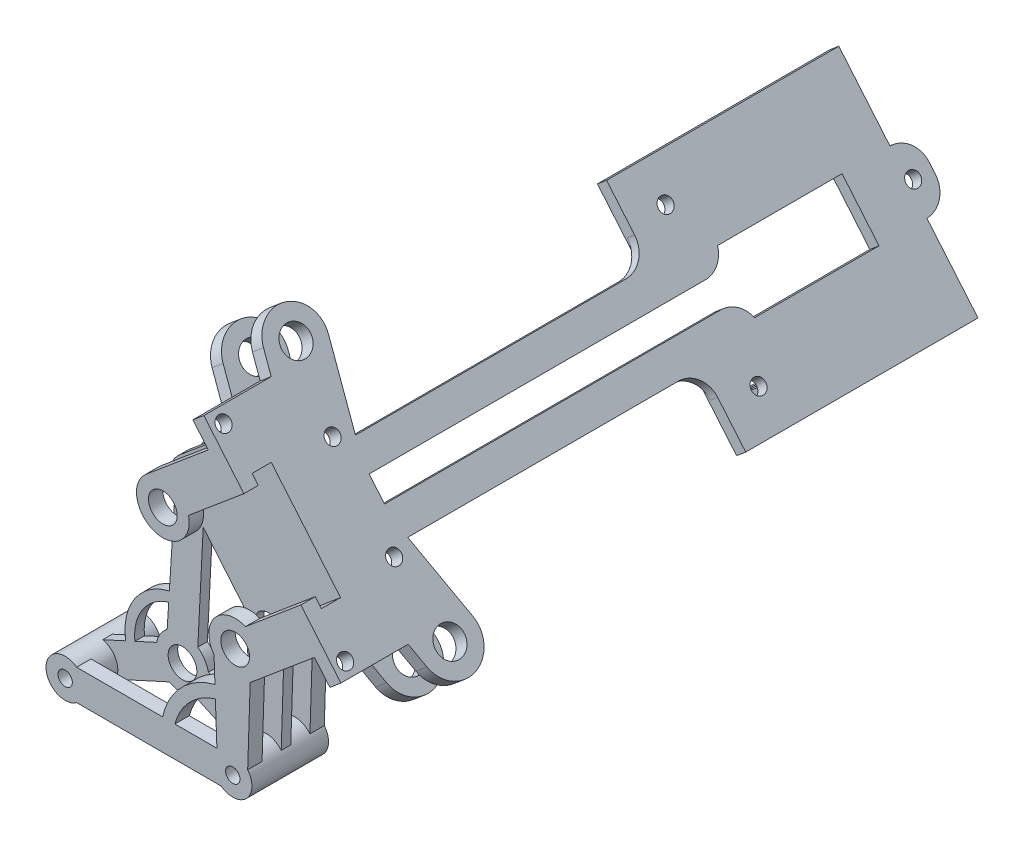
SolidWorks part; units mm, degrees
ref_plane "Front Plane" through (0, 0, 0) normal (0, 0, 1) x (1, 0, 0)
ref_plane "Top Plane" through (0, 0, 0) normal (0, 1, 0) x (1, 0, 0)
ref_plane "Right Plane" through (0, 0, 0) normal (1, 0, 0) x (0, 0, -1)
sketch "Sketch1" plane through (0, 0, 0) normal (0, 0, 1) x (1, 0, 0)
  line L0 (0, 0) -> (0, 8) construction
  line L1 (0, 8) -> (18.002, 23.1055) construction
  line L2 (2.8965, 41.1076) -> (18.002, 23.1055) construction
  circle A1 centre (2.8965, 41.1076) radius 3
  circle A3 centre (0, 8) radius 2.5
  circle A4 centre (-17.5, 0) radius 2.1
  circle A5 centre (17.5, 0) radius 2.1
  circle A6 centre (18.002, 23.1055) radius 3
  dimension "D1" = 5
  dimension "D2" = 8
  dimension "D5" = 6
  dimension "D6" = 6
  dimension "D3" = 50
  dimension "D4" = 23.5
  dimension "D7" = 23.5
  dimension "D8" = 90
sketch "Sketch2" plane through (0, 0, 0) normal (0, 0, 1) x (1, 0, 0)
  circle A0 centre (-17.5, 0) radius 4
  circle A1 centre (17.5, 0) radius 4
  circle A2 centre (17.5, 0) radius 1.5
  circle A3 centre (-17.5, 0) radius 1.5
  dimension "D2" = 8
  dimension "D3" = 8
  dimension "D4" = 3
  dimension "D5" = 3
extrude "Boss-Extrude1" add sketch "Sketch2" along normal blind 7
sketch "Sketch3" plane through (0, 0, 7) normal (0, 0, 1) x (1, 0, 0)
  line L0 (21.5374, 18.8923) -> (36.8583, 31.748)
  line L1 (36.8583, 31.748) -> (14.6821, 58.1765)
  line L2 (14.6821, 58.1765) -> (-0.6388, 45.3208)
  line L3 (2.8965, 41.1076) -> (18.002, 23.1055) construction
  line L4 (12.7408, 24.7084) -> (4.3263, 34.7365)
  line L5 (21.8764, 27.0092) -> (29.9374, 33.7731)
  line L6 (8.1578, 39.5046) -> (17.3371, 28.5652)
  line L7 (29.9374, 33.7731) -> (15.4746, 51.0091)
  line L8 (15.4746, 51.0091) -> (7.4137, 44.2452)
  line L9 (18.002, 23.1055) -> (17.5, 0) construction
  line L10 (21.1372, 18.5866) -> (20.6119, 2.5132)
  line L11 (13.4856, 19.9667) -> (14.1163, 5.0654)
  line L13 (-3.2, 12.4733) -> (-2.8753, 17.5777)
  line L14 (3.2, 12.4733) -> (4.3263, 34.7365)
  line L15 (0, 8) -> (17.5, 0) construction
  line L16 (5.3987, 9.0505) -> (14.1163, 5.0654)
  line L17 (2.7379, 3.2299) -> (13.9868, -1.9125)
  line L18 (-17.5, 0) -> (0, 8) construction
  line L19 (-16.6477, 3.9081) -> (-11.8489, 6.1019)
  line L20 (-13.9868, -1.9125) -> (-2.7379, 3.2299)
  line L21 (-9.947, 6.9713) -> (-5.3987, 9.0505)
  line L22 (-2.7414, 19.6827) -> (-1.5817, 37.9146)
  circle A0 centre (18.002, 23.1055) radius 3
  circle A2 centre (0, 8) radius 3
  arc A3 (12.7408, 24.7084) -> (13.4856, 19.9667) centre (18.002, 23.1055) ccw
  arc A4 (5.3987, 9.0505) -> (3.2, 12.4733) centre (0, 8) ccw
  arc A5 (8.1578, 39.5046) -> (7.4137, 44.2452) centre (2.8965, 41.1076) ccw
  circle A6 centre (17.5, 0) radius 4 construction
  circle A7 centre (-17.5, 0) radius 4 construction
  arc A8 (13.9868, -1.9125) -> (20.6119, 2.5132) centre (17.5, 0) ccw
  arc A9 (-16.6477, 3.9081) -> (-13.9868, -1.9125) centre (-17.5, 0) ccw
  circle A10 centre (-17.5, 0) radius 1.5 construction
  circle A11 centre (17.5, 0) radius 1.5 construction
  circle A12 centre (-17.5, 0) radius 1.5
  circle A13 centre (17.5, 0) radius 1.5
  arc A22 (-2.7414, 19.6827) -> (-11.8489, 6.1019) centre (0, 8) ccw
  arc A23 (-2.8753, 17.5777) -> (-9.947, 6.9713) centre (0, 8) ccw
  arc A24 (-3.2, 12.4733) -> (-5.3987, 9.0505) centre (0, 8) ccw
  circle A25 centre (0, 8) radius 5.5 construction
  arc A26 (-2.7379, 3.2299) -> (2.7379, 3.2299) centre (0, 8) ccw
  arc A27 (-0.6388, 45.3208) -> (-1.5817, 37.9146) centre (2.8965, 41.1076) ccw
  circle A28 centre (2.8965, 41.1076) radius 3
  circle A29 centre (18.002, 23.1055) radius 5.5 construction
  arc A30 (21.8764, 27.0092) -> (17.3371, 28.5652) centre (18.002, 23.1055) ccw
  arc A31 (21.1372, 18.5866) -> (21.5374, 18.8923) centre (18.002, 23.1055) ccw
  point P14 (22.117, 24.617)
  point P26 (5.5, 41.234)
  point P33 (5.5, 8)
  point P41 (17.0585, 12.3085)
  point P46 (0, 24.617)
  point P51 (8.75, 4)
  point P57 (-8.75, 4)
  circle M4 centre (17.5, 0) radius 4
  circle M5 centre (17.5, 0) radius 1.5
  dimension "D1" = 6
  dimension "D2" = 6
  dimension "D3" = 6
  dimension "D17" = 10
  dimension "D18" = 12
  dimension "D7" = 3
  dimension "D8" = 3
  dimension "D9" = 4
  dimension "D10" = 6
  dimension "D11" = 6
  dimension "D12" = 20
  dimension "D4" = 2.5
  dimension "D5" = 2.5
extrude "Boss-Extrude2" add sketch "Sketch3" along normal blind 2 contours L10 A31 L0 L1 L2 A27 L22 A22 L19 A9 L20 A26 L17 L5 A30 L6 A5 L8 L7 L13 A24 L21 A23 L16 A4 L14 L4 A3 L11 A0 A28 A2 A12 M4 | M4 M5 | A30 L5 L7 L8 A5 L6 region at (20.8231, 19.4125, 7) region at (21.1648, 1.295, 7) region at (17.9351, 38.3879, 7)
ref_plane "Plane1" through (0, 0, 13) normal (0, 0, 1) x (1, 0, 0)
sketch "Sketch6" plane through (0, 0, 13) normal (0, 0, 1) x (1, 0, 0)
  line L0 (21.5374, 18.8923) -> (36.8583, 31.748)
  line L1 (36.8583, 31.748) -> (31.716, 37.8764)
  line L2 (36.8583, 31.748) -> (14.6821, 58.1765) construction
  line L3 (31.716, 37.8764) -> (20.1479, 28.1696)
  line L4 (-0.6388, 45.3208) -> (14.6821, 58.1765)
  line L5 (14.6821, 58.1765) -> (19.8244, 52.0482)
  line L6 (19.8244, 52.0482) -> (8.2563, 42.3414)
  line L7 (17.5, 0) -> (-17.5, 0) construction
  line L10 (17.5, 0) -> (18.002, 23.1055) construction
  line L12 (20.6119, 2.5132) -> (21.1372, 18.5866)
  line L13 (15.1, -3.2) -> (-15.1, -3.2)
  line L15 (14.1832, 3.2) -> (13.8689, 11.961)
  line L16 (14.1832, 3.2) -> (5.4165, 3.2)
  line L17 (2.8453, 3.2) -> (-15.1, 3.2)
  line L18 (13.7767, 14.5306) -> (13.5868, 19.8259)
  arc A0 (21.1372, 18.5866) -> (13.5868, 19.8259) centre (18.002, 23.1055) ccw
  circle A1 centre (18.002, 23.1055) radius 3
  circle A2 centre (2.8965, 41.1076) radius 5.5
  circle A3 centre (2.8965, 41.1076) radius 3
  arc A4 (15.1, -3.2) -> (20.6119, 2.5132) centre (17.5, 0) ccw
  circle A5 centre (17.5, 0) radius 1.5
  circle A6 centre (-17.5, 0) radius 1.5
  arc A8 (12.7408, 24.7084) -> (13.4856, 19.9667) centre (18.002, 23.1055) ccw construction
  arc A9 (-0.6388, 45.3208) -> (-1.5817, 37.9146) centre (2.8965, 41.1076) ccw construction
  arc A16 (13.8689, 11.961) -> (5.4165, 3.2) centre (17.5, 0) ccw
  arc A17 (13.7767, 14.5306) -> (2.8453, 3.2) centre (17.5, 0) ccw
  arc A18 (-15.1, 3.2) -> (-15.1, -3.2) centre (-17.5, 0) ccw
  point P37 (0, 0)
  point P41 (17.0585, 12.3085)
  dimension "D3" = 15
  dimension "D4" = 12.5
  dimension "D5" = 3.2
  dimension "D7" = 4
  dimension "D8" = 8
  dimension "D1" = 8
  dimension "D2" = 8
  dimension "D6" = 3.2
extrude "Boss-Extrude4" add sketch "Sketch6" along normal blind 3 separate body contours L18 A17 L17 L13 A4 L12 A0 A1 A5 A6 A16 L15 L16 | A0 L0 L1 L3 | A2 L6 L5 L4 | A2 A3 region at (28.4532, 29.7435, 13) region at (21.0034, 19.1765, 13) region at (11.2485, 50.2472, 13) region at (4.5939, 46.1753, 13)
sketch "Sketch7" plane through (0, 0, 9) normal (0, 0, 1) x (1, 0, 0)
  line L4 (28.4053, 32.4876) -> (33.0015, 36.3443)
  line L5 (36.8583, 31.748) -> (14.6821, 58.1765) construction
  line L6 (33.0015, 36.3443) -> (36.8583, 31.748)
  line L7 (36.8583, 31.748) -> (32.262, 27.8913)
  line L10 (21.5374, 18.8923) -> (36.8583, 31.748) construction
  line L11 (32.262, 27.8913) -> (28.4053, 32.4876)
  line L12 (14.6821, 58.1765) -> (10.0858, 54.3198)
  line L13 (14.6821, 58.1765) -> (-0.6388, 45.3208) construction
  line L14 (10.0858, 54.3198) -> (13.9426, 49.7236)
  line L15 (13.9426, 49.7236) -> (18.5388, 53.5803)
  line L16 (18.5388, 53.5803) -> (14.6821, 58.1765)
  circle A0 centre (17.5, 0) radius 1.5 construction
  circle A1 centre (-17.5, 0) radius 1.5 construction
  circle A3 centre (17.5, 0) radius 1.5
  circle A4 centre (-17.5, 0) radius 1.5
  circle A6 centre (-17.5, 0) radius 4
  circle A7 centre (17.5, 0) radius 4
  dimension "D1" = 6
  dimension "D2" = 6
  dimension "D3" = 6
extrude "Boss-Extrude5" add sketch "Sketch7" along normal up to surface (4 mm away) up to face at (21.002, 23.1055, 13)
sketch "Sketch8" plane through (0, 0, 0) normal (0, 0, 1) x (1, 0, 0)
  line L0 (14.6821, 58.1765) -> (36.8583, 31.748)
  line L1 (36.8583, 31.748) -> (21.1372, 18.5866)
  line L2 (20.6119, 2.5132) -> (21.1372, 18.5866)
  line L3 (13.4856, 19.9667) -> (14.2329, 2.3079)
  line L4 (13.4856, 19.9667) -> (14.1163, 5.0654) construction
  line L5 (12.7408, 24.7084) -> (3.5615, 35.6479)
  line L7 (12.7408, 24.7084) -> (4.3263, 34.7365) construction
  line L8 (14.6821, 58.1765) -> (-0.6388, 45.3208)
  line L12 (2.8965, 41.1076) -> (18.002, 23.1055) construction
  line L13 (6.7533, 36.5113) -> (14.1453, 27.7018)
  line L14 (5.9444, 46.2758) -> (13.1016, 52.2815)
  line L15 (13.1016, 52.2815) -> (30.7783, 31.2152)
  line L16 (30.7783, 31.2152) -> (23.621, 25.2096)
  circle A0 centre (2.8965, 41.1076) radius 3
  circle A1 centre (18.002, 23.1055) radius 3
  arc A2 (-0.6388, 45.3208) -> (3.5615, 35.6479) centre (2.8965, 41.1076) ccw
  arc A3 (12.7408, 24.7084) -> (13.4856, 19.9667) centre (18.002, 23.1055) ccw
  arc A4 (20.6119, 2.5132) -> (14.2329, 2.3079) centre (17.5, 0) ccw
  circle A5 centre (17.5, 0) radius 4 construction
  arc A6 (-0.6388, 45.3208) -> (-1.5817, 37.9146) centre (2.8965, 41.1076) ccw construction
  arc A7 (12.7408, 24.7084) -> (13.4856, 19.9667) centre (18.002, 23.1055) ccw construction
  arc A10 (21.1372, 18.5866) -> (21.8992, 19.2245) centre (18.002, 23.1055) ccw
  arc A11 (6.7533, 36.5113) -> (5.9444, 46.2758) centre (2.8965, 41.1076) ccw
  arc A12 (14.1453, 27.7018) -> (23.621, 25.2096) centre (18.002, 23.1055) cw
  dimension "D1" = 6
  dimension "D2" = 6
  dimension "D3" = 5
  dimension "D4" = 3.5
  dimension "D5" = 2
extrude "Boss-Extrude6" add sketch "Sketch8" along normal blind 3 contours A4 L2 L1 L0 L8 A2 L5 A3 L3 A1 A0 region at (25.2462, 44.5226, 0)
sketch "Sketch9" plane through (37.2622, 31.2667, 0) normal (0.766, 0.6428, 0) x (0, 0, -1)
  line L5 (-7, 0.6284) -> (-7, 35.1284) construction
  line L9 (-7, 35.1284) -> (-7, 0.6284)
  line L10 (0, 17.8784) -> (-7, 17.8784) construction
  line L11 (0, 35.1284) -> (0, 0.6284) construction
  line L12 (5, 42.8784) -> (0, 24.1313) construction
  line L13 (10.7973, 41.3322) -> (5.8134, 22.6451)
  line L14 (-0.7973, 44.4246) -> (-1.9432, 40.1284)
  line L16 (-16, 35.1284) -> (-7, 35.1284)
  line L17 (-16, 35.1284) -> (-16, 40.1284)
  line L18 (-16, 40.1284) -> (-1.9432, 40.1284)
  line L20 (-16, 0.6284) -> (-16, -4.3716)
  line L21 (-16, -4.3716) -> (-1.9432, -4.3716)
  line L22 (-0.7973, -8.6678) -> (-1.9432, -4.3716)
  line L23 (10.7973, -5.5754) -> (5.8134, 13.1116)
  line L24 (-16, 0.6284) -> (-7, 0.6284)
  line L29 (5.8134, 22.6451) -> (5.8134, 13.1116)
  circle A0 centre (5, 42.8784) radius 3
  arc A1 (10.7973, 41.3322) -> (-0.7973, 44.4246) centre (5, 42.8784) ccw
  circle A3 centre (-13.5, 37.6284) radius 1.5
  circle A4 centre (-13.5, -1.8716) radius 1.5
  arc A5 (10.7973, -5.5754) -> (-0.7973, -8.6678) centre (5, -7.1216) cw
  circle A6 centre (5, -7.1216) radius 3
  circle A7 centre (3, 27.8784) radius 1.5
  circle A8 centre (3, 7.8784) radius 1.5
  point P14 (2.5, 33.5048)
  point P35 (5.3917, 17.8784)
  dimension "D1" = 6
  dimension "D4" = 6
  dimension "D5" = 3
  dimension "D9" = 3
  dimension "D2" = 25
  dimension "D3" = 5
  dimension "D6" = 2.5
  dimension "D7" = 5
  dimension "D8" = 2.5
  dimension "D10" = 10
  dimension "D11" = 3
extrude "Boss-Extrude8" add sketch "Sketch9" against normal blind 3
sketch "Sketch10" plane through (0, 0, -5.8134) normal (0, 0, -1) x (-1, 0, 0)
  line L0 (-23.472, 43.0339) -> (-25.7702, 44.9623) construction
  line L1 (-26.536, 39.3824) -> (-20.4081, 46.6854) construction
  line L2 (-28.8342, 41.3108) -> (-22.7062, 48.6138) construction
  line L3 (-24.1632, 46.8774) -> (-22.6311, 45.5918)
  line L4 (-22.6311, 45.5918) -> (-18.7744, 50.1881)
  line L5 (-18.7744, 50.1881) -> (-20.3065, 51.4737)
  line L6 (-20.3065, 51.4737) -> (-24.1632, 46.8774)
  line L7 (-29.7018, 37.1653) -> (-31.2339, 38.4509)
  line L8 (-25.8451, 41.7616) -> (-29.7018, 37.1653)
  line L9 (-27.3771, 43.0472) -> (-25.8451, 41.7616)
  line L10 (-31.2339, 38.4509) -> (-27.3771, 43.0472)
  dimension "D1" = 2
  dimension "D2" = 6
  dimension "D3" = 2.5
extrude "Boss-Extrude9" add sketch "Sketch10" along normal blind 75
ref_plane "Plane2" through (-11.492, 13.6956, 0) normal (0.6428, -0.766, 0) x (-0.766, -0.6428, 0)
ref_plane "Plane3" through (-1.4645, 1.7453, 0) normal (0.6428, -0.766, 0) x (-0.766, -0.6428, 0)
sketch "Sketch11" plane through (-1.4645, 1.7453, 0) normal (0.6428, -0.766, 0) x (-0.766, -0.6428, 0)
  line L0 (-48.6423, 80.8134) -> (-48.6423, 6.8091) construction
  line L1 (-48.6423, 112.8134) -> (-35.6423, 112.8134)
  line L2 (-48.6423, 112.8134) -> (-48.6423, 78.8134)
  line L3 (-48.6423, 78.8134) -> (-35.6423, 78.8134)
  line L4 (-35.6423, 112.8134) -> (-35.6423, 78.8134)
  line L5 (-48.6423, 95.8134) -> (-35.6423, 95.8134) construction
  line L6 (-35.6423, 84.5634) -> (-45.6423, 84.5634)
  line L7 (-45.6423, 84.5634) -> (-45.6423, 107.0634)
  line L8 (-45.6423, 107.0634) -> (-35.6423, 107.0634)
  circle A0 centre (-39.6423, 81.8134) radius 1.5
  circle A1 centre (-39.6423, 109.8134) radius 1.5
  dimension "D3" = 3
  dimension "D1" = 6
  dimension "D2" = 14
  dimension "D4" = 3
  dimension "D5" = 3
  dimension "D6" = 4
  dimension "D7" = 90
  dimension "D8" = 22.5
extrude "Boss-Extrude10" add sketch "Sketch11" along normal blind 3 separate body contours L5 L2 L3 L4 L6 L7 A0 | L2 L5 L7 L8 L4 L1 A1 region at (32.2263, 30.0153, -107.1188) region at (32.2263, 30.0153, -84.5079)
ref_plane "Plane4" through (37.2622, 31.2667, 0) normal (0.766, 0.6428, 0) x (0, 0, -1)
sketch "Sketch12" plane through (37.2622, 31.2667, 0) normal (0.766, 0.6428, 0) x (0, 0, -1)
  line L0 (116.8134, 23.8784) -> (121.8134, 23.8784)
  line L5 (80.8134, 20.3784) -> (80.8134, 15.3784) construction
  line L14 (116.8134, -4.7216) -> (68.3134, -4.7216)
  line L15 (116.8134, -4.7216) -> (116.8134, 11.8784)
  line L16 (106.8134, 11.8784) -> (68.3134, 11.8784)
  line L17 (68.3134, -4.7216) -> (68.3134, 11.8784)
  line L18 (80.8134, 15.3784) -> (80.8134, 17.8784) construction
  line L19 (80.8134, 17.8784) -> (121.8134, 17.8784) construction
  line L20 (-3.8082, 17.8784) -> (3.8082, 17.8784) construction
  line L21 (80.8134, 15.3784) -> (5.8134, 15.3784) construction
  line L22 (80.8134, 15.3784) -> (80.8134, 9.3784) construction
  line L23 (112.8134, -0.7216) -> (78.8134, -0.7216) construction
  line L24 (112.8134, -0.7216) -> (112.8134, 2.2784) construction
  line L25 (68.3134, 40.4784) -> (68.3134, 23.8784)
  line L26 (116.8134, 11.8784) -> (121.8134, 11.8784)
  line L27 (106.8134, 11.8784) -> (106.8134, 23.8784)
  line L29 (121.8134, 11.8784) -> (121.8134, 23.8784)
  line L30 (106.8134, 23.8784) -> (68.3134, 23.8784)
  line L31 (116.8134, 40.4784) -> (116.8134, 23.8784)
  line L32 (116.8134, 40.4784) -> (68.3134, 40.4784)
  circle A0 centre (117.8134, 17.8784) radius 1.5
  circle A1 centre (75.8134, 32.9784) radius 1.5
  circle A2 centre (75.8134, 2.7784) radius 1.5
  point P26 (106.8134, 17.8784)
  dimension "D7" = 3
  dimension "D8" = 3
  dimension "D1" = 3.5
  dimension "D2" = 12.5
  dimension "D3" = 4
  dimension "D4" = 4
  dimension "D5" = 15
  dimension "D6" = 5
  dimension "D9" = 4
  dimension "D10" = 7.5
  dimension "D11" = 7.5
extrude "Boss-Extrude11" add sketch "Sketch12" against normal blind 2.5
fillet "Fillet1" radius 5 6 edges at (30.4678, 37.8081, -68.3134) (19.5404, 50.8309, -68.3134) (28.6693, 39.5625, -121.8134) (20.9559, 48.7551, -121.8134) (23.3972, 46.2346, -80.8134) (26.6111, 42.4044, -80.8134)
ref_plane "Plane5" through (28.8357, 24.196, 0) normal (-0.766, -0.6428, 0) x (0, 0, 1)
sketch "Sketch13" plane through (28.8357, 24.196, 0) normal (-0.766, -0.6428, 0) x (0, 0, 1)
  line L0 (-5, 42.8784) -> (-2.042, 31.7877) construction
  line L1 (0.7973, 44.4246) -> (3, 36.1659)
  line L2 (-10.7973, 41.3322) -> (-8.2093, 31.6284)
  line L3 (-5.8134, 22.6451) -> (-10.7973, 41.3322) construction
  line L4 (3, 35.1284) -> (3, 36.1659)
  line L5 (3, 35.1284) -> (0, 35.1284)
  line L6 (0, 35.1284) -> (0, 31.6284)
  line L10 (0, 31.6284) -> (-8.2093, 31.6284)
  line L12 (3, 31.6284) -> (0, 31.6284) construction
  line L13 (-3.8082, 17.8784) -> (3.8082, 17.8784) construction
  line L14 (3, 0.6284) -> (3, -0.4092)
  line L15 (0.7973, -8.6678) -> (3, -0.4092)
  line L16 (-10.7973, -5.5754) -> (-8.2093, 4.1284)
  line L17 (0, 4.1284) -> (-8.2093, 4.1284)
  line L18 (0, 0.6284) -> (0, 4.1284)
  line L19 (3, 0.6284) -> (0, 0.6284)
  circle A0 centre (-5, 42.8784) radius 3
  arc A1 (0.7973, 44.4246) -> (-10.7973, 41.3322) centre (-5, 42.8784) ccw
  circle A3 centre (-5, -7.1216) radius 3
  arc A4 (0.7973, -8.6678) -> (-10.7973, -5.5754) centre (-5, -7.1216) cw
  point P3 (-3.521, 37.333)
  dimension "D1" = 0
extrude "Boss-Extrude12" add sketch "Sketch13" along normal blind 3
sketch "Sketch14" plane through (28.8357, 24.196, 0) normal (-0.766, -0.6428, 0) x (0, 0, 1)
  line L0 (0, 31.6284) -> (-8.2093, 31.6284)
  line L1 (-8.2093, 31.6284) -> (-9.0094, 34.6284)
  line L2 (-10.7973, 41.3322) -> (-8.2093, 31.6284) construction
  line L3 (-9.0094, 34.6284) -> (0, 34.6284)
  line L4 (0, 31.6284) -> (0, 35.1284) construction
  line L5 (0, 34.6284) -> (0, 31.6284)
  line L6 (-3.8082, 17.8784) -> (3.8082, 17.8784) construction
  line L7 (-9.0094, 1.1284) -> (0, 1.1284)
  line L8 (-8.2093, 4.1284) -> (-9.0094, 1.1284)
  line L9 (0, 4.1284) -> (-8.2093, 4.1284)
  line L10 (0, 1.1284) -> (0, 4.1284)
  dimension "D1" = 3
  dimension "D2" = 3
extrude "Boss-Extrude13" add sketch "Sketch14" against normal up to surface (8 mm away) up to face at (30.8641, 34.2244, -3)
sketch "Sketch15" plane through (37.2622, 31.2667, 0) normal (0.766, 0.6428, 0) x (0, 0, -1)
  line L0 (5.8134, 15.3784) -> (5.8134, 20.3784) construction
  line L1 (76.0437, 20.3784) -> (5.8134, 20.3784) construction
  line L2 (76.0437, 15.3784) -> (5.8134, 15.3784) construction
  line L3 (106.8134, 23.8784) -> (106.8134, 11.8784) construction
  line L4 (106.8134, 11.8784) -> (80.8134, 11.8784) construction
  line L5 (80.8134, 23.8784) -> (106.8134, 23.8784) construction
  line L6 (5.8134, 15.3784) -> (5.8134, 20.3784)
  line L7 (76.0437, 20.3784) -> (5.8134, 20.3784)
  line L8 (76.0437, 15.3784) -> (5.8134, 15.3784)
  line L9 (106.8134, 23.8784) -> (106.8134, 11.8784)
  line L10 (106.8134, 11.8784) -> (80.8134, 11.8784)
  line L11 (80.8134, 23.8784) -> (106.8134, 23.8784)
  line L24 (116.8134, -4.7216) -> (116.8134, 11.8784)
  line L25 (121.8134, 16.8784) -> (121.8134, 18.8784)
  line L26 (116.8134, 23.8784) -> (116.8134, 40.4784)
  line L27 (116.8134, 40.4784) -> (68.3134, 40.4784)
  line L28 (68.3134, 40.4784) -> (68.3134, 31.3784)
  line L29 (63.3134, 26.3784) -> (6.8091, 26.3784)
  line L30 (6.8091, 26.3784) -> (10.7973, 41.3322)
  line L31 (-0.7973, 44.4246) -> (-1.9432, 40.1284)
  line L32 (-1.9432, 40.1284) -> (-16, 40.1284)
  line L33 (-16, 40.1284) -> (-16, 27.1284)
  line L34 (-16, 27.1284) -> (-13, 27.1284)
  line L35 (-13, 27.1284) -> (-13, 29.1284)
  line L36 (-13, 29.1284) -> (-9, 29.1284)
  line L37 (-9, 29.1284) -> (-9, 6.6284)
  line L38 (-9, 6.6284) -> (-13, 6.6284)
  line L39 (-13, 6.6284) -> (-13, 8.6284)
  line L40 (-13, 8.6284) -> (-16, 8.6284)
  line L41 (-16, 8.6284) -> (-16, -4.3716)
  line L42 (-16, -4.3716) -> (-1.9432, -4.3716)
  line L43 (-1.9432, -4.3716) -> (-0.7973, -8.6678)
  line L44 (10.7973, -5.5754) -> (6.8091, 9.3784)
  line L45 (6.8091, 9.3784) -> (63.3134, 9.3784)
  line L46 (68.3134, 4.3784) -> (68.3134, -4.7216)
  line L47 (68.3134, -4.7216) -> (116.8134, -4.7216)
  line L48 (116.8134, -4.7216) -> (116.8134, 11.8784)
  line L49 (121.8134, 16.8784) -> (121.8134, 18.8784)
  line L50 (116.8134, 23.8784) -> (116.8134, 40.4784)
  line L51 (116.8134, 40.4784) -> (68.3134, 40.4784)
  line L52 (68.3134, 40.4784) -> (68.3134, 31.3784)
  line L53 (63.3134, 26.3784) -> (6.8091, 26.3784)
  line L54 (6.8091, 26.3784) -> (10.7973, 41.3322)
  line L55 (-0.7973, 44.4246) -> (-1.9432, 40.1284)
  line L56 (-1.9432, 40.1284) -> (-16, 40.1284)
  line L57 (-16, 40.1284) -> (-16, 27.1284)
  line L58 (-16, 27.1284) -> (-13, 27.1284)
  line L59 (-13, 27.1284) -> (-13, 29.1284)
  line L60 (-13, 29.1284) -> (-9, 29.1284)
  line L61 (-9, 29.1284) -> (-9, 6.6284)
  line L62 (-9, 6.6284) -> (-13, 6.6284)
  line L63 (-13, 6.6284) -> (-13, 8.6284)
  line L64 (-13, 8.6284) -> (-16, 8.6284)
  line L65 (-16, 8.6284) -> (-16, -4.3716)
  line L66 (-16, -4.3716) -> (-1.9432, -4.3716)
  line L67 (-1.9432, -4.3716) -> (-0.7973, -8.6678)
  line L68 (10.7973, -5.5754) -> (6.8091, 9.3784)
  line L69 (6.8091, 9.3784) -> (63.3134, 9.3784)
  line L70 (68.3134, 4.3784) -> (68.3134, -4.7216)
  line L71 (68.3134, -4.7216) -> (116.8134, -4.7216)
  arc A0 (76.0437, 20.3784) -> (80.8134, 23.8784) centre (76.0437, 25.3784) ccw construction
  arc A1 (80.8134, 11.8784) -> (76.0437, 15.3784) centre (76.0437, 10.3784) ccw construction
  circle A2 centre (117.8134, 17.8784) radius 1.5 construction
  circle A3 centre (75.8134, 2.7784) radius 1.5 construction
  circle A4 centre (75.8134, 32.9784) radius 1.5 construction
  circle A5 centre (-13.5, 37.6284) radius 1.5 construction
  arc A6 (116.8134, 11.8784) -> (121.8134, 16.8784) centre (116.8134, 16.8784) ccw
  arc A7 (121.8134, 18.8784) -> (116.8134, 23.8784) centre (116.8134, 18.8784) ccw
  arc A8 (63.3134, 26.3784) -> (68.3134, 31.3784) centre (63.3134, 31.3784) ccw
  arc A9 (10.7973, 41.3322) -> (-0.7973, 44.4246) centre (5, 42.8784) ccw
  arc A10 (-0.7973, -8.6678) -> (10.7973, -5.5754) centre (5, -7.1216) ccw
  arc A11 (68.3134, 4.3784) -> (63.3134, 9.3784) centre (63.3134, 4.3784) ccw
  arc A12 (116.8134, 11.8784) -> (121.8134, 16.8784) centre (116.8134, 16.8784) ccw
  arc A13 (121.8134, 18.8784) -> (116.8134, 23.8784) centre (116.8134, 18.8784) ccw
  arc A14 (63.3134, 26.3784) -> (68.3134, 31.3784) centre (63.3134, 31.3784) ccw
  arc A15 (10.7973, 41.3322) -> (-0.7973, 44.4246) centre (5, 42.8784) ccw
  arc A16 (-0.7973, -8.6678) -> (10.7973, -5.5754) centre (5, -7.1216) ccw
  arc A17 (68.3134, 4.3784) -> (63.3134, 9.3784) centre (63.3134, 4.3784) ccw
  circle A18 centre (-13.5, -1.8716) radius 1.5 construction
  circle A19 centre (5, 42.8784) radius 3 construction
  circle A20 centre (3, 27.8784) radius 1.5 construction
  circle A21 centre (3, 7.8784) radius 1.5 construction
  circle A22 centre (5, -7.1216) radius 3 construction
  arc A23 (76.0437, 20.3784) -> (80.8134, 23.8784) centre (76.0437, 25.3784) ccw
  arc A24 (80.8134, 11.8784) -> (76.0437, 15.3784) centre (76.0437, 10.3784) ccw
  circle A25 centre (117.8134, 17.8784) radius 1.5
  circle A26 centre (75.8134, 2.7784) radius 1.5
  circle A27 centre (75.8134, 32.9784) radius 1.5
  circle A28 centre (-13.5, 37.6284) radius 1.5
  circle A29 centre (-13.5, -1.8716) radius 1.5
  circle A30 centre (5, 42.8784) radius 3
  circle A31 centre (3, 27.8784) radius 1.5
  circle A32 centre (3, 7.8784) radius 1.5
  circle A33 centre (5, -7.1216) radius 3
  dimension "D1" = 0
